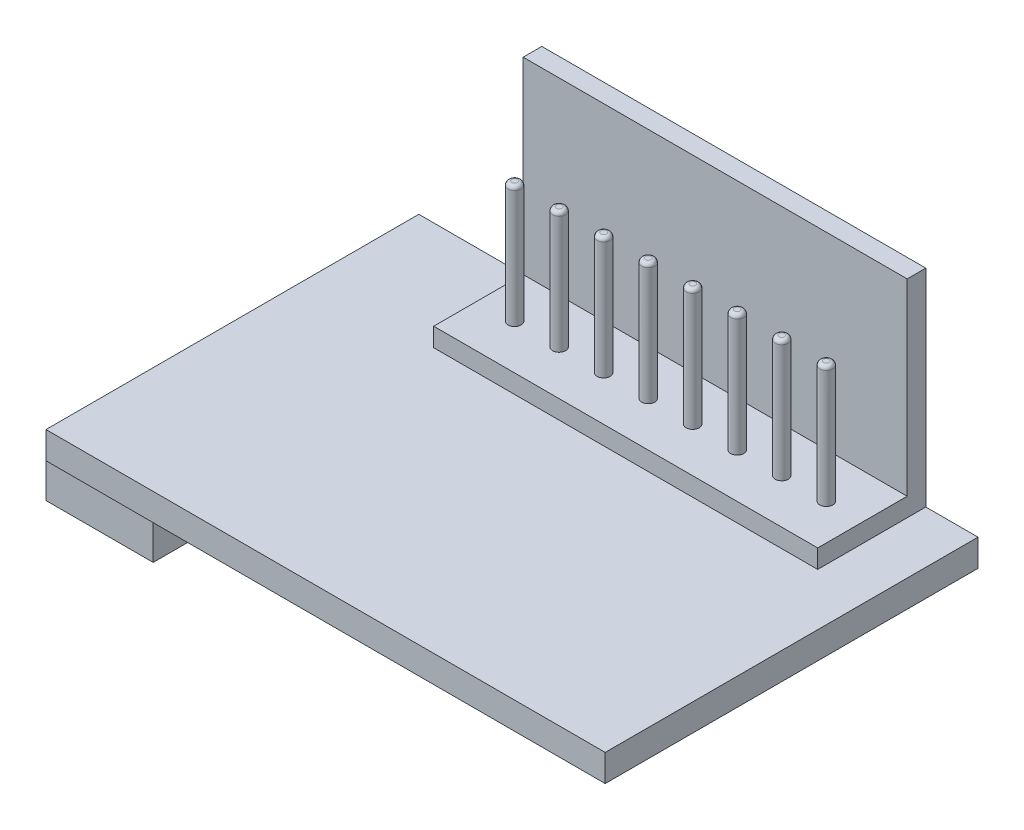
SolidWorks part; units mm, degrees
ref_plane "Front" through (0, 0, 0) normal (0, 0, 1) x (1, 0, 0)
ref_plane "Top" through (0, 0, 0) normal (0, 1, 0) x (1, 0, 0)
ref_plane "Right" through (0, 0, 0) normal (1, 0, 0) x (0, 0, -1)
sketch "Sketch1" plane through (0, 0, 0) normal (0, 1, 0) x (1, 0, 0)
  line L1 (0, 0) -> (30, 0)
  line L2 (0, 0) -> (0, 20)
  line L3 (0, 20) -> (30, 20)
  line L4 (30, 0) -> (30, 20)
  dimension "D1" = 30
  dimension "D2" = 20
extrude "Boss-Extrude1" add sketch "Sketch1" along normal blind 1.45
sketch "Sketch2" plane through (0, 1.45, 0) normal (0, 1, 0) x (1, 0, 0)
  line L0 (30, 20) -> (0, 20) construction
  line L1 (6.6, 20) -> (27.2, 20)
  line L2 (6.6, 20) -> (6.6, 14.2)
  line L3 (6.6, 14.2) -> (27.2, 14.2)
  line L4 (27.2, 20) -> (27.2, 14.2)
  line L6 (0, 20) -> (0, 0) construction
  dimension "D1" = 6.6
  dimension "D2" = 20.6
  dimension "D3" = 5.8
extrude "Boss-Extrude2" add sketch "Sketch2" along normal blind 11.1
sketch "Sketch4" plane through (0, 0, 0) normal (0, -1, 0) x (1, 0, 0)
  line L1 (-1, -1) -> (4.75, -1)
  line L2 (-1, -1) -> (-1, -16.5)
  line L3 (-1, -16.5) -> (4.75, -16.5)
  line L4 (4.75, -1) -> (4.75, -16.5)
  line L5 (0, -20) -> (0, 0) construction
  line L6 (0, 0) -> (30, 0) construction
  dimension "D1" = 1
  dimension "D2" = 15.5
  dimension "D3" = 5.75
  dimension "D4" = 1
extrude "Boss-Extrude3" add sketch "Sketch4" along normal blind 2.85
sketch "Sketch5" plane through (0, 0, -14.2) normal (0, 0, 1) x (1, 0, 0)
  line L0 (27.2, 12.55) -> (27.2, 1.45) construction
  line L1 (6.6, 12.55) -> (27.2, 12.55)
  line L2 (6.6, 12.55) -> (6.6, 2.45)
  line L3 (6.6, 2.45) -> (27.2, 2.45)
  line L4 (27.2, 12.55) -> (27.2, 2.45)
  line L5 (6.6, 1.45) -> (27.2, 1.45) construction
  dimension "D1" = 1
extrude "Cut-Extrude1" cut sketch "Sketch5" against normal offset from surface (4.8 mm away) 1 up to face at (16.5375, 5.25, -20)
sketch "Sketch6" plane through (0, 2.45, 0) normal (0, 1, 0) x (1, 0, 0)
  line L0 (6.6, 16.6) -> (27.2, 16.6) construction
  line L1 (6.6, 19) -> (6.6, 14.2) construction
  line L2 (27.2, 19) -> (27.2, 14.2) construction
  line L3 (16.9, 19) -> (16.9, 14.2) construction
  line L4 (27.2, 19) -> (6.6, 19) construction
  line L5 (6.6, 14.2) -> (27.2, 14.2) construction
  circle A0 centre (8.5394, 16.6) radius 0.35
  circle A1 centre (10.9282, 16.6) radius 0.35
  circle A2 centre (13.3169, 16.6) radius 0.35
  circle A3 centre (15.7056, 16.6) radius 0.35
  circle A4 centre (18.0944, 16.6) radius 0.35
  circle A5 centre (20.4831, 16.6) radius 0.35
  circle A6 centre (22.8718, 16.6) radius 0.35
  circle A7 centre (25.2606, 16.6) radius 0.35
  dimension "D1" = 0.7
  dimension "D2" = 8
extrude "Boss-Extrude4" add sketch "Sketch6" along normal blind 6.52
fillet "Fillet1" radius 0.2 8 edges at (25.2606, 8.97, -16.25) (22.8718, 8.97, -16.25) (20.4831, 8.97, -16.25) (18.0944, 8.97, -16.25) (15.7056, 8.97, -16.25) (13.3169, 8.97, -16.25) (10.9282, 8.97, -16.25) (8.5394, 8.97, -16.25)
